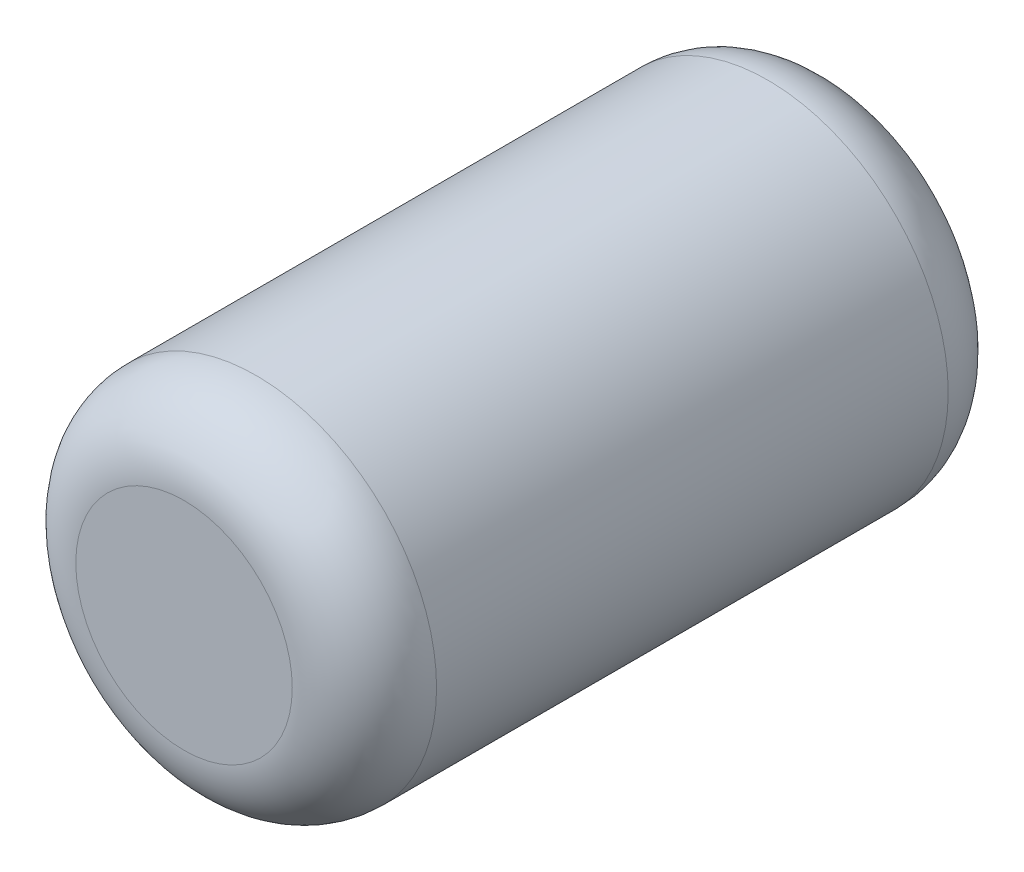
SolidWorks part; units mm, degrees
ref_plane "Front Plane" through (0, 0, 0) normal (0, 0, 1) x (1, 0, 0)
ref_plane "Top Plane" through (0, 0, 0) normal (0, 1, 0) x (1, 0, 0)
ref_plane "Right Plane" through (0, 0, 0) normal (1, 0, 0) x (0, 0, -1)
sketch "Sketch1" plane through (0, 0, 0) normal (0, 0, 1) x (1, 0, 0)
  circle A0 centre (0, 0) radius 34.925
extrude "Boss-Extrude1" add sketch "Sketch1" along normal blind 127
fillet "Fillet1" radius 13.97 2 edges at (34.925, 0, 127) (34.925, 0, 0)
